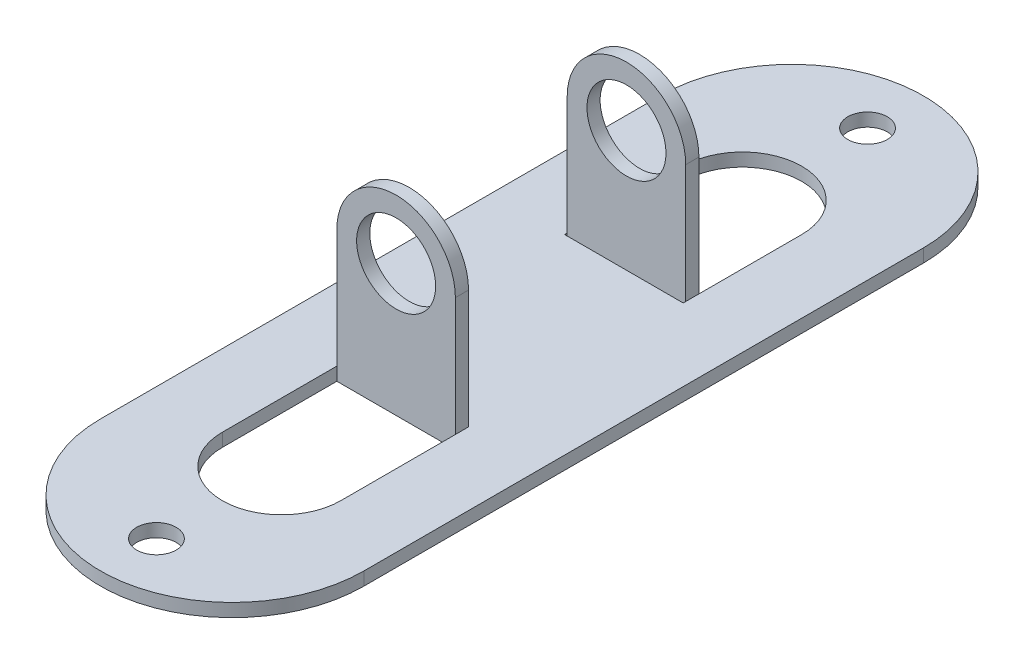
SolidWorks part; units mm, degrees
material "AISI 1020 Steel, Cold Rolled"
ref_plane "Front Plane" through (0, 0, 0) normal (0, 0, 1) x (1, 0, 0)
ref_plane "Top Plane" through (0, 0, 0) normal (0, 1, 0) x (1, 0, 0)
ref_plane "Right Plane" through (0, 0, 0) normal (1, 0, 0) x (0, 0, -1)
sketch "Sketch2" plane through (0, 0, 0) normal (0, 1, 0) x (1, 0, 0)
  line L0 (0, 27.0999) -> (0, -57.9001) construction
  line L1 (20, 27.0999) -> (20, -57.9001)
  line L2 (-20, 27.0999) -> (-20, -57.9001)
  arc A0 (20, 27.0999) -> (-20, 27.0999) centre (0, 27.0999) ccw
  arc A1 (-20, -57.9001) -> (20, -57.9001) centre (0, -57.9001) ccw
  point P3 (0, -15.4001)
  point P15 (0, 9.2437)
  dimension "D1" = 85
  dimension "D2" = 40
base flange "Base-Flange1" sketch "Sketch2" thickness 2 reverse thickness direction no parameters "D1"=10
sketch "Sketch9" plane through (0, 0, 0) normal (0, 1, 0) x (1, 0, 0)
  line L0 (9, 1.5999) -> (-9, 1.5999)
  line L1 (-9, -32.4001) -> (9, -32.4001)
  line L2 (-9, 1.5999) -> (-9, 19.5999)
  line L3 (9, 1.5999) -> (9, 19.5999)
  line L4 (-9, -32.4001) -> (-9, -50.4001)
  line L5 (9, -32.4001) -> (9, -50.4001)
  arc A0 (-9, 19.5999) -> (9, 19.5999) centre (0, 19.5999) cw
  arc A1 (9, -50.4001) -> (-9, -50.4001) centre (0, -50.4001) cw
  arc A2 (20, 27.0999) -> (-20, 27.0999) centre (0, 27.0999) ccw construction
  arc A3 (-20, -57.9001) -> (20, -57.9001) centre (0, -57.9001) ccw construction
  dimension "D7" = 7.5
  dimension "D8" = 7.5
  dimension "D1" = 18
  dimension "D2" = 18
  dimension "D3" = 18
  dimension "D4" = 18
  dimension "D5" = 34
  dimension "D6" = 18
extrude "Cut-Extrude13" cut sketch "Sketch9" against normal blind 10
ref_plane "Plane2" through (0, 0, 31) normal (0, 0, 1) x (1, 0, 0)
sketch "Sketch16" plane through (0, 0, 31) normal (0, 0, 1) x (1, 0, 0)
  line L0 (-9, -2) -> (-9, 18)
  line L1 (9, -2) -> (9, 18)
  line L2 (-9, -2) -> (9, -2)
  arc A0 (9, 18) -> (-9, 18) centre (0, 18) ccw
  dimension "D1" = 20
  dimension "D2" = 20
extrude "Boss-Extrude4" add sketch "Sketch16" along normal blind 2
ref_plane "Plane4" through (0, 0, -1.985) normal (0, 0, 1) x (1, 0, 0)
sketch "Sketch17" plane through (0, 0, -1.985) normal (0, 0, 1) x (1, 0, 0)
  line L0 (9, -2) -> (9, 18)
  line L1 (-9, -2) -> (-9, 18)
  line L2 (9, -2) -> (-9, -2)
  arc A0 (9, 18) -> (-9, 18) centre (0, 18) ccw
  dimension "D1" = 20
  dimension "D2" = 20
extrude "Boss-Extrude5" add sketch "Sketch17" against normal blind 2
sketch "Sketch18" plane through (0, 0, 33) normal (0, 0, 1) x (1, 0, 0)
  circle A0 centre (0, 18) radius 6
extrude "Cut-Extrude14" cut sketch "Sketch18" against normal through all
sketch "Sketch19" plane through (0, -2, 0) normal (0, -1, 0) x (1, 0, 0)
  circle A0 centre (0, 69.4001) radius 3
  circle A1 centre (0, -38.5999) radius 3
  arc A2 (-9, -19.5999) -> (9, -19.5999) centre (0, -19.5999) ccw construction
  arc A3 (9, 50.4001) -> (-9, 50.4001) centre (0, 50.4001) ccw construction
  point P4 (0, -28.5999)
  point P8 (0, 59.4001)
  dimension "D1" = 6
  dimension "D2" = 6
  dimension "D3" = 10
  dimension "D4" = 10
extrude "Cut-Extrude15" cut sketch "Sketch19" against normal through all
sketch "Bend-Lines1" [suppressed] plane through (0, 0, 0) normal (0, 1, 0) x (1, 0, 0)
sketch "Bounding-Box1" [suppressed] plane through (0, 0, 0) normal (0, 1, 0) x (1, 0, 0)
sheet metal parameters "Sheet-Metal1" thickness 2 parameters "D1"=10
flat pattern "Flat-Pattern1" [suppressed]
sketch "Bend-Lines2" plane through (0, 0, 0) normal (0, 1, 0) x (1, 0, 0)
sketch3d "Bounding-Box2" [suppressed]
  line L0 (-20, 20, 0) -> (-20, -105, 0) construction
  line L1 (20, 20, 0) -> (20, -105, 0) construction
  line L2 (-20, 20, 0) -> (20, 20, 0) construction
  line L3 (-20, -105, 0) -> (20, -105, 0) construction
sheet metal parameters "Sheet-Metal4" thickness 2 parameters "D1"=10
flat pattern "Flat-Pattern1"
sketch "Bend-Lines2" plane through (0, 0, 0) normal (0, 1, 0) x (1, 0, 0)
sketch3d "Bounding-Box2" [suppressed]
  line L0 (-20, 20, 0) -> (-20, -105, 0) construction
  line L1 (20, 20, 0) -> (20, -105, 0) construction
  line L2 (-20, 20, 0) -> (20, 20, 0) construction
  line L3 (-20, -105, 0) -> (20, -105, 0) construction
sheet metal parameters "Sheet-Metal6" thickness 2 parameters "D1"=10
flat pattern "Flat-Pattern1"
sketch "Bend-Lines2" plane through (0, 0, 0) normal (0, 1, 0) x (1, 0, 0)
sketch3d "Bounding-Box2" [suppressed]
  line L0 (-20, 20, 0) -> (-20, -105, 0) construction
  line L1 (20, 20, 0) -> (20, -105, 0) construction
  line L2 (-20, 20, 0) -> (20, 20, 0) construction
  line L3 (-20, -105, 0) -> (20, -105, 0) construction
sheet metal parameters "Sheet-Metal7" thickness 2 parameters "D1"=10
flat pattern "Flat-Pattern1"
sketch "Bend-Lines2" plane through (0, 0, 0) normal (0, 1, 0) x (1, 0, 0)
sketch3d "Bounding-Box2" [suppressed]
  line L0 (-20, 20, 0) -> (-20, -105, 0) construction
  line L1 (20, 20, 0) -> (20, -105, 0) construction
  line L2 (-20, 20, 0) -> (20, 20, 0) construction
  line L3 (-20, -105, 0) -> (20, -105, 0) construction
sheet metal parameters "Sheet-Metal8" thickness 2 parameters "D1"=10
flat pattern "Flat-Pattern1"
sketch "Bend-Lines2" plane through (0, 0, 0) normal (0, 1, 0) x (1, 0, 0)
sketch3d "Bounding-Box2" [suppressed]
  line L0 (-20, 20, 0) -> (-20, -105, 0) construction
  line L1 (20, 20, 0) -> (20, -105, 0) construction
  line L2 (-20, 20, 0) -> (20, 20, 0) construction
  line L3 (-20, -105, 0) -> (20, -105, 0) construction
sheet metal parameters "Sheet-Metal9" thickness 2 parameters "D1"=10
flat pattern "Flat-Pattern1"
sketch "Bend-Lines2" plane through (0, 0, 0) normal (0, 1, 0) x (1, 0, 0)
sketch3d "Bounding-Box2" [suppressed]
  line L0 (-20, 20, 0) -> (-20, -105, 0) construction
  line L1 (20, 20, 0) -> (20, -105, 0) construction
  line L2 (-20, 20, 0) -> (20, 20, 0) construction
  line L3 (-20, -105, 0) -> (20, -105, 0) construction
